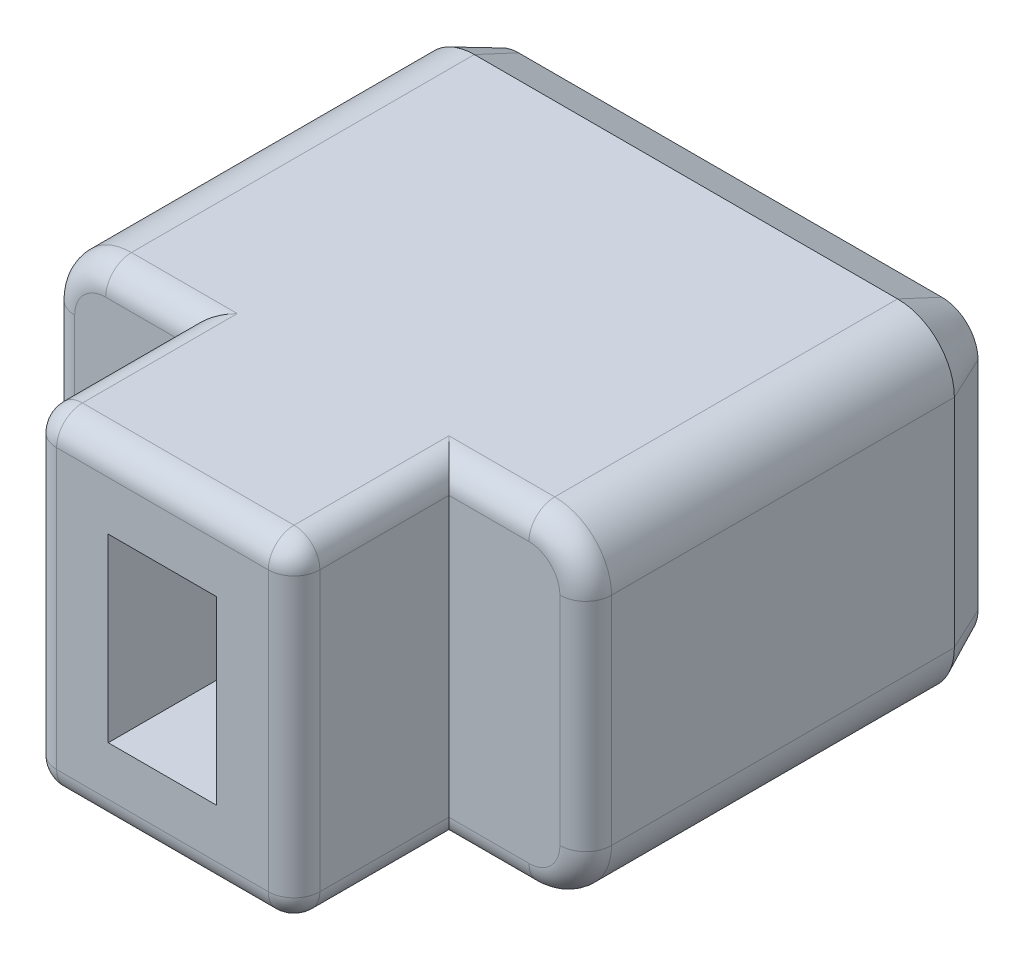
SolidWorks part; units mm, degrees
ref_plane "Plan de face" through (0, 0, 0) normal (0, 0, 1) x (1, 0, 0)
ref_plane "Plan de dessus" through (0, 0, 0) normal (0, 1, 0) x (1, 0, 0)
ref_plane "Plan de droite" through (0, 0, 0) normal (1, 0, 0) x (0, 0, -1)
sketch "Esquisse2" plane through (0, 0, 0) normal (0, 0, 1) x (1, 0, 0)
  line L1 (1.1, 0) -> (9.3, 0)
  line L2 (0, 1.1) -> (0, 5.3)
  line L3 (1.1, 6.4) -> (9.3, 6.4)
  line L4 (10.4, 1.1) -> (10.4, 5.3)
  arc A0 (9.3, 6.4) -> (10.4, 5.3) centre (9.3, 5.3) cw
  arc A1 (9.3, 0) -> (10.4, 1.1) centre (9.3, 1.1) ccw
  arc A2 (1.1, 0) -> (0, 1.1) centre (1.1, 1.1) cw
  arc A3 (0, 5.3) -> (1.1, 6.4) centre (1.1, 5.3) cw
  point P7 (10.4, 6.4)
  point P12 (0, 0)
  point P15 (0, 6.4)
  dimension "D3" = 1.1
  dimension "D1" = 10.4
  dimension "D2" = 6.4
extrude "Boss.-Extru.1" add sketch "Esquisse2" along normal blind 11
sketch "Esquisse3" plane through (0, 0, 11) normal (0, 0, 1) x (1, 0, 0)
  line L0 (0, 5.3) -> (0, 1.1) construction
  line L1 (4.15, 4.95) -> (6.25, 4.95)
  line L2 (4.15, 4.95) -> (4.15, 1.45)
  line L3 (4.15, 1.45) -> (6.25, 1.45)
  line L4 (6.25, 4.95) -> (6.25, 1.45)
  line L5 (10.4, 1.1) -> (10.4, 5.3) construction
  line L6 (9.3, 6.4) -> (1.1, 6.4) construction
  line L7 (1.1, 0) -> (9.3, 0) construction
  dimension "D1" = 2.1
  dimension "D2" = 3.5
  dimension "D3" = 4.15
  dimension "D4" = 4.15
  dimension "D5" = 1.45
  dimension "D6" = 1.45
extrude "Enlèv. mat.-Extru.1" cut sketch "Esquisse3" against normal blind 3
sketch "Esquisse4" plane through (0, 0, 11) normal (0, 0, 1) x (1, 0, 0)
  line L0 (2.65, 6.4) -> (2.65, 0)
  line L1 (9.3, 6.4) -> (1.1, 6.4) construction
  line L2 (1.1, 0) -> (9.3, 0) construction
  line L3 (2.65, 0) -> (7.75, 0)
  line L4 (7.75, 0) -> (7.75, 6.4)
  line L5 (7.75, 6.4) -> (2.65, 6.4)
  line L6 (4.15, 4.95) -> (4.15, 1.45) construction
  line L7 (6.25, 1.45) -> (6.25, 4.95) construction
  dimension "D1" = 1.5
  dimension "D2" = 1.5
extrude "Enlèv. mat.-Extru.2" cut sketch "Esquisse4" against normal blind 3 flip side to cut
fillet "Congé1" radius 0.5 18 edges at (8.525, 0, 8) (10.0778, 0.3222, 8) (10.4, 3.2, 8) (10.0778, 6.0778, 8) (1.875, 6.4, 8) (0.3222, 6.0778, 8) (1.875, 0, 8) (0.3222, 0.3222, 8) (7.75, 6.4, 9.5) (2.65, 6.4, 9.5) (7.75, 0, 9.5) (2.65, 0, 9.5) (2.65, 3.2, 11) (5.2, 6.4, 11) (7.75, 3.2, 11) (5.2, 0, 11) (8.525, 6.4, 8) (0, 3.2, 8)
chamfer "Chanfrein1" distance 0.4 angle 65 8 edges at (5.2, 0, 0) (10.0778, 0.3222, 0) (0.3222, 0.3222, 0) (10.4, 3.2, 0) (0, 3.2, 0) (10.0778, 6.0778, 0) (0.3222, 6.0778, 0) (5.2, 6.4, 0) first distance on face at (5.2, 3.2, 0)
sketch "Esquisse5" plane through (0, 0, 0) normal (0, 0, -1) x (-1, 0, 0)
  line L0 (-0.4, 5.3) -> (-10, 5.3) construction
  arc A0 (-9.3, 6) -> (-10, 5.3) centre (-9.3, 5.3) ccw construction
  text T0 "2" font "Century Gothic" height 4
extrude "Enlèv. mat.-Extru.3" cut sketch "Esquisse5" against normal blind 0.3
extrude "Boss.-Extru.2" add sketch "Esquisse5<2>" along normal blind 0.3 separate body
sketch "Esquisse5<2>" plane through (0, 0, 0) normal (0, 0, -1) x (-1, 0, 0) same geometry as "Esquisse5"
